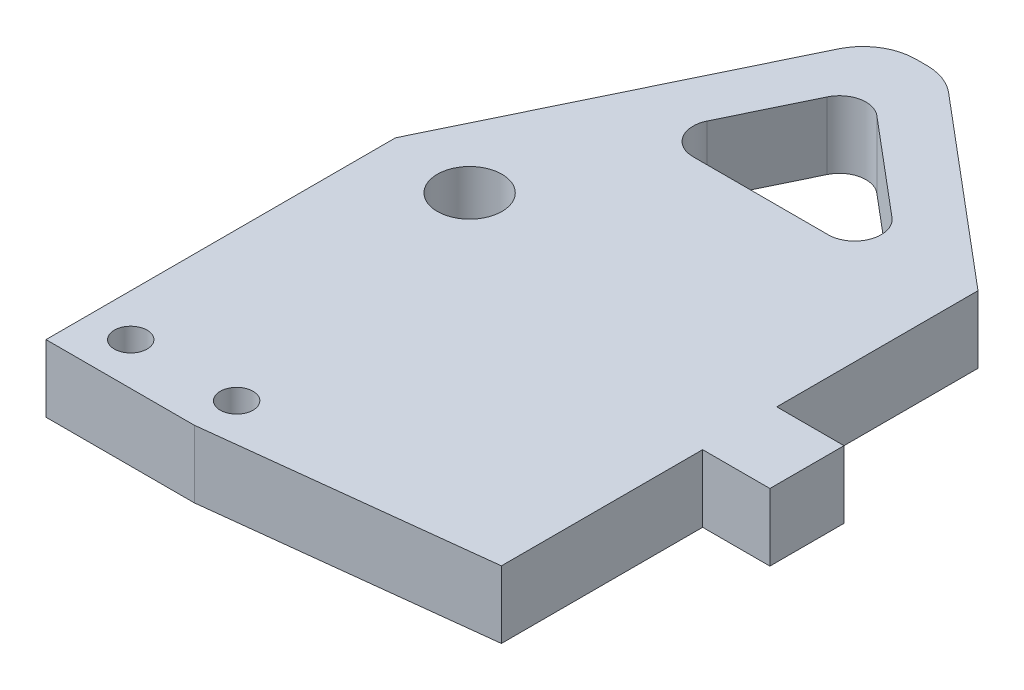
SolidWorks part; units mm, degrees
material "6061 Alloy"
ref_plane "Front Plane" through (0, 0, 0) normal (0, 0, 1) x (1, 0, 0)
ref_plane "Top Plane" through (0, 0, 0) normal (0, 1, 0) x (1, 0, 0)
ref_plane "Right Plane" through (0, 0, 0) normal (1, 0, 0) x (0, 0, -1)
sketch "Sketch1" plane through (0, 0, 0) normal (0, 1, 0) x (1, 0, 0)
  line L1 (-80, 0) -> (-80, 60)
  line L7 (0, 0) -> (-52, -6)
  line L8 (-52, -6) -> (-80, -6)
  line L9 (-80, -6) -> (-80, 0)
  line L10 (-80, 60) -> (-50, 122)
  line L11 (-50, 122) -> (-38, 122)
  line L12 (-38, 122) -> (0, 90)
  line L13 (0, 90) -> (0, 52)
  line L14 (0, 52) -> (12.7, 52)
  line L15 (12.7, 52) -> (12.7, 38)
  line L16 (12.7, 38) -> (0, 38)
  line L17 (0, 38) -> (0, 0)
  circle A0 centre (-64, 58) radius 6.1
  circle A3 centre (-72, 2) radius 3.1
  circle A4 centre (-52, 2) radius 3.1
  dimension "D8" = 12.2
  dimension "D11" = 38
  dimension "D12" = 6.2
  dimension "D16" = 6.2
  dimension "D1" = 80
  dimension "D2" = 90
  dimension "D3" = 60
  dimension "D4" = 62
  dimension "D5" = 30
  dimension "D6" = 12
  dimension "D7" = 38
  dimension "D9" = 16
  dimension "D10" = 6
  dimension "D13" = 8
  dimension "D14" = 8
  dimension "D15" = 20
  dimension "D17" = 58
  dimension "D18" = 12.7
extrude "Boss-Extrude1" add sketch "Sketch1" along normal blind 12.7
fillet "Fillet1" radius 10 2 edges at (-38, 6.35, -122) (-50, 6.35, -122)
sketch "Sketch3" plane through (0, 12.7, 0) normal (0, 1, 0) x (1, 0, 0)
  line L5 (-9.5872, 85) -> (-43.1274, 113.2444)
  line L6 (-43.1274, 113.2444) -> (-56.7941, 85)
  line L7 (-56.7941, 85) -> (-9.5872, 85)
  line L10 (0, 90) -> (-35.2083, 119.6491) construction
  line L11 (-52.7312, 116.3556) -> (-80, 60) construction
  dimension "D1" = 10
  dimension "D2" = 10
  dimension "D3" = 10
  dimension "D4" = 10
  dimension "D5" = 5
extrude "Cut-Extrude1" cut sketch "Sketch3" against normal through all
fillet "Fillet2" radius 5 3 edges at (-43.1274, 6.35, -113.2444) (-9.5872, 6.35, -85) (-56.7941, 6.35, -85)
